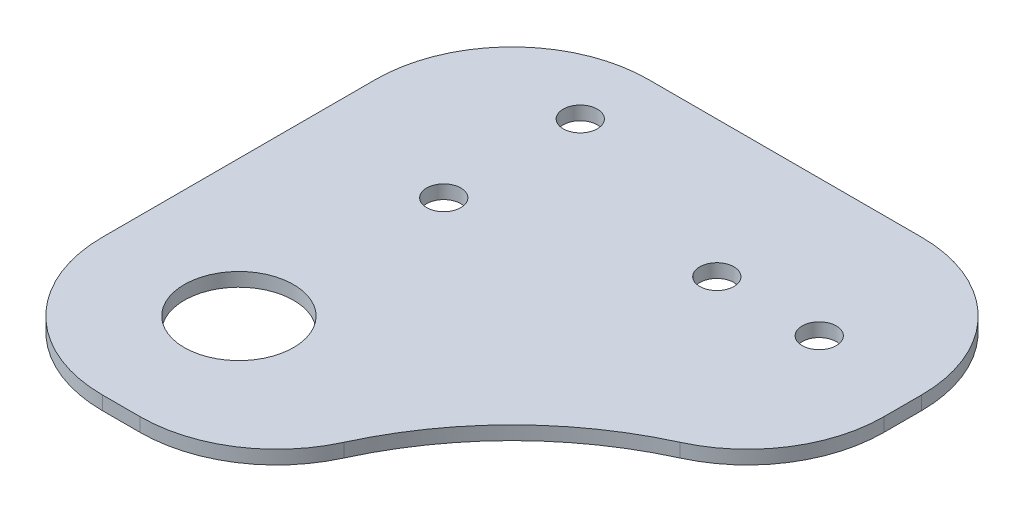
SolidWorks part; units mm, degrees
ref_plane "Plan de face" through (0, 0, 0) normal (0, 0, 1) x (1, 0, 0)
ref_plane "Plan de dessus" through (0, 0, 0) normal (0, 1, 0) x (1, 0, 0)
ref_plane "Plan de droite" through (0, 0, 0) normal (1, 0, 0) x (0, 0, -1)
sketch "Sketch1" plane through (0, 0, 0) normal (0, 1, 0) x (1, 0, 0)
  line L1 (80, 40) -> (0, 40)
  line L2 (80, 40) -> (80, 0)
  line L3 (80, 0) -> (0, 0)
  line L4 (0, 40) -> (0, 0)
  line L5 (0, 0) -> (40, 0)
  line L6 (0, 0) -> (0, -40)
  line L7 (0, -40) -> (40, -40)
  line L8 (40, 0) -> (40, -40)
  circle A0 centre (20, 10) radius 2.5
  circle A1 centre (65, 20) radius 2.5
  circle A2 centre (50, 20) radius 2.5
  circle A3 centre (20, 30) radius 2.5
  circle A8 centre (20, -20) radius 8
  point P15 (0, 20)
  point P30 (20, -40)
  point P32 (0, -20)
  dimension "D3" = 5
  dimension "D4" = 5
  dimension "D5" = 5
  dimension "D9" = 5
  dimension "D14" = 16
  dimension "D1" = 40
  dimension "D2" = 80
  dimension "D6" = 20
  dimension "D7" = 10
  dimension "D8" = 15
  dimension "D10" = 10
  dimension "D12" = 40
  dimension "D13" = 40
extrude "Boss-Extrude1" add sketch "Sketch1" along normal blind 2 contours L1 L4 L3 L2 A3 A2 A1 A0 | L8 L3 L6 L7 region at (40.0315, 0, -20) region at (20, 0, 0.5657)
fillet "Fillet1" radius 50 1 edges at (40, 1, 0)
fillet "Fillet2" radius 20 5 edges at (0, 1, -40) (80, 1, 0) (80, 1, -40) (0, 1, 40) (40, 1, 40)
